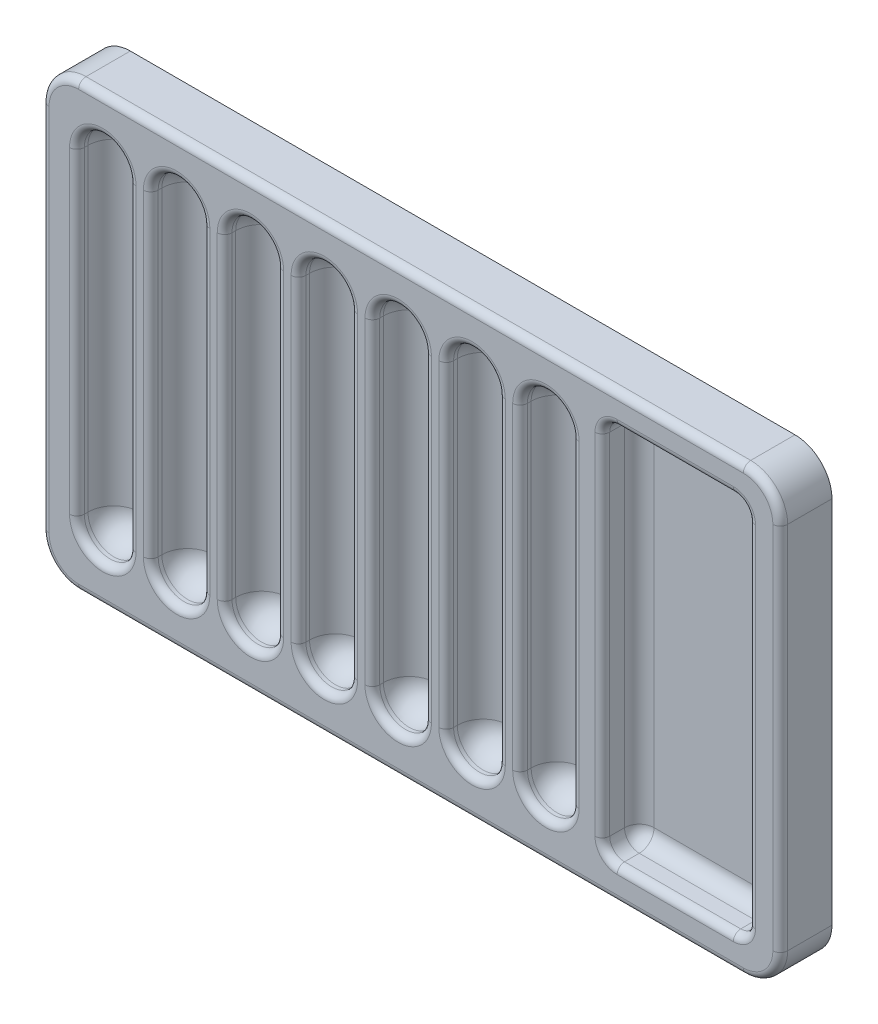
SolidWorks part; units mm, degrees
ref_plane "Front Plane" through (0, 0, 0) normal (0, 0, 1) x (1, 0, 0)
ref_plane "Top Plane" through (0, 0, 0) normal (0, 1, 0) x (1, 0, 0)
ref_plane "Right Plane" through (0, 0, 0) normal (1, 0, 0) x (0, 0, -1)
sketch "Sketch1" plane through (0, 0, 0) normal (0, 0, 1) x (1, 0, 0)
  line L1 (0, 0) -> (10, 0)
  line L2 (0, 0) -> (0, -6)
  line L3 (0, -6) -> (10, -6)
  line L4 (10, 0) -> (10, -6)
  dimension "D1" = 10
  dimension "D2" = 6
extrude "Boss-Extrude1" add sketch "Sketch1" along normal blind 0.7
sketch "Sketch2" plane through (0, 0, 0.7) normal (0, 0, 1) x (1, 0, 0)
  line L0 (0.827, -0.8427) -> (0.827, -5.1427) construction
  line L1 (1.177, -0.8427) -> (1.177, -5.1427)
  line L2 (0.477, -0.8427) -> (0.477, -5.1427)
  arc A0 (1.177, -0.8427) -> (0.477, -0.8427) centre (0.827, -0.8427) ccw
  arc A1 (0.477, -5.1427) -> (1.177, -5.1427) centre (0.827, -5.1427) ccw
  point P2 (0.827, -2.9927)
  dimension "D1" = 0.7
  dimension "D2" = 4.3
extrude "Cut-Extrude1" cut sketch "Sketch2" against normal blind 0.5
fillet "Fillet4" radius 0.35 4 edges at (1.177, -2.9927, 0.2) (0.827, -5.4927, 0.2) (0.477, -2.9927, 0.2) (0.827, -0.4927, 0.2)
fillet "Fillet5" radius 0.1 4 edges at (0.827, -0.4927, 0.7) (1.177, -2.9927, 0.7) (0.827, -5.4927, 0.7) (0.477, -2.9927, 0.7)
pattern_linear "LPattern4" count 7 spacing 1 along (1, 0, 0) of "Cut-Extrude1", "Fillet4", "Fillet5"
fillet "Fillet6" radius 0.5 4 edges at (10, -6, 0.35) (10, 0, 0.35) (0, 0, 0.35) (0, -6, 0.35)
fillet "Fillet7" radius 0.1 8 edges at (0.1464, -5.8536, 0.7) (0, -3, 0.7) (0.1464, -0.1464, 0.7) (5, 0, 0.7) (9.8536, -0.1464, 0.7) (10, -3, 0.7) (9.8536, -5.8536, 0.7) (5, -6, 0.7)
sketch "Sketch3" plane through (0, 0, 0.7) normal (0, 0, 1) x (1, 0, 0)
  line L1 (7.5912, -0.4239) -> (9.5647, -0.4239)
  line L2 (7.5912, -0.4239) -> (7.5912, -5.5611)
  line L3 (7.5912, -5.5611) -> (9.5647, -5.5611)
  line L4 (9.5647, -0.4239) -> (9.5647, -5.5611)
extrude "Cut-Extrude2" cut sketch "Sketch3" against normal blind 0.5
fillet "Fillet8" radius 0.2 4 edges at (9.5647, -5.5611, 0.45) (7.5912, -5.5611, 0.45) (9.5647, -0.4239, 0.45) (7.5912, -0.4239, 0.45)
fillet "Fillet9" radius 0.2 8 edges at (7.6498, -5.5025, 0.2) (7.5912, -2.9925, 0.2) (7.6498, -0.4825, 0.2) (8.5779, -0.4239, 0.2) (9.5061, -0.4825, 0.2) (9.5647, -2.9925, 0.2) (9.5061, -5.5025, 0.2) (8.5779, -5.5611, 0.2)
fillet "Fillet10" radius 0.1 8 edges at (7.6498, -0.4825, 0.7) (8.5779, -0.4239, 0.7) (9.5061, -0.4825, 0.7) (9.5647, -2.9925, 0.7) (9.5061, -5.5025, 0.7) (7.5912, -2.9925, 0.7) (7.6498, -5.5025, 0.7) (8.5779, -5.5611, 0.7)
